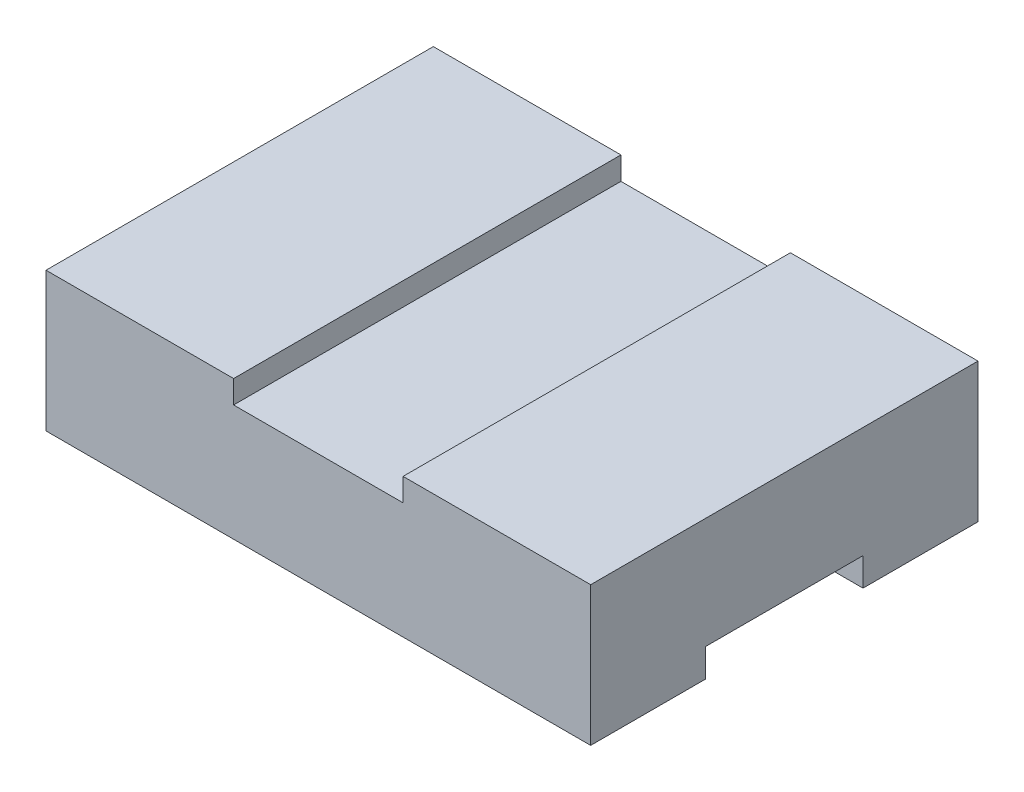
SolidWorks part; units mm, degrees
ref_plane "Front Plane" through (0, 0, 0) normal (0, 0, 1) x (1, 0, 0)
ref_plane "Top Plane" through (0, 0, 0) normal (0, 1, 0) x (1, 0, 0)
ref_plane "Right Plane" through (0, 0, 0) normal (1, 0, 0) x (0, 0, -1)
sketch "Sketch1" plane through (0, 0, 0) normal (0, 1, 0) x (1, 0, 0)
  line L1 (-45, -32) -> (45, -32)
  line L2 (-45, -32) -> (-45, 32)
  line L3 (-45, 32) -> (45, 32)
  line L4 (45, -32) -> (45, 32)
  line L5 (-45, -32) -> (45, 32) construction
  line L6 (-45, 32) -> (45, -32) construction
  point P0 (0, 0)
  dimension "D1" = 90
  dimension "D2" = 64
extrude "Boss-Extrude1" add sketch "Sketch1" along normal blind 23
sketch "Sketch3" plane through (-45, 0, 0) normal (-1, 0, 0) x (0, 0, 1)
  line L1 (-13, -4.6588) -> (13, -4.6588)
  line L2 (-13, -4.6588) -> (-13, 4.6588)
  line L3 (-13, 4.6588) -> (13, 4.6588)
  line L4 (13, -4.6588) -> (13, 4.6588)
  line L5 (-13, -4.6588) -> (13, 4.6588) construction
  line L6 (-13, 4.6588) -> (13, -4.6588) construction
  point P0 (0, 0)
  dimension "D1" = 26
extrude "Cut-Extrude1" cut sketch "Sketch3" against normal through all
sketch "Sketch4" plane through (0, 0, 32) normal (0, 0, 1) x (1, 0, 0)
  line L0 (-45, 23) -> (45, 23) construction
  line L1 (-14, 19.2147) -> (14, 19.2147)
  line L2 (-14, 19.2147) -> (-14, 26.7853)
  line L3 (-14, 26.7853) -> (14, 26.7853)
  line L4 (14, 19.2147) -> (14, 26.7853)
  line L5 (-14, 19.2147) -> (14, 26.7853) construction
  line L6 (-14, 26.7853) -> (14, 19.2147) construction
  point P0 (0, 23)
  dimension "D1" = 28
extrude "Cut-Extrude2" cut sketch "Sketch4" against normal through all
